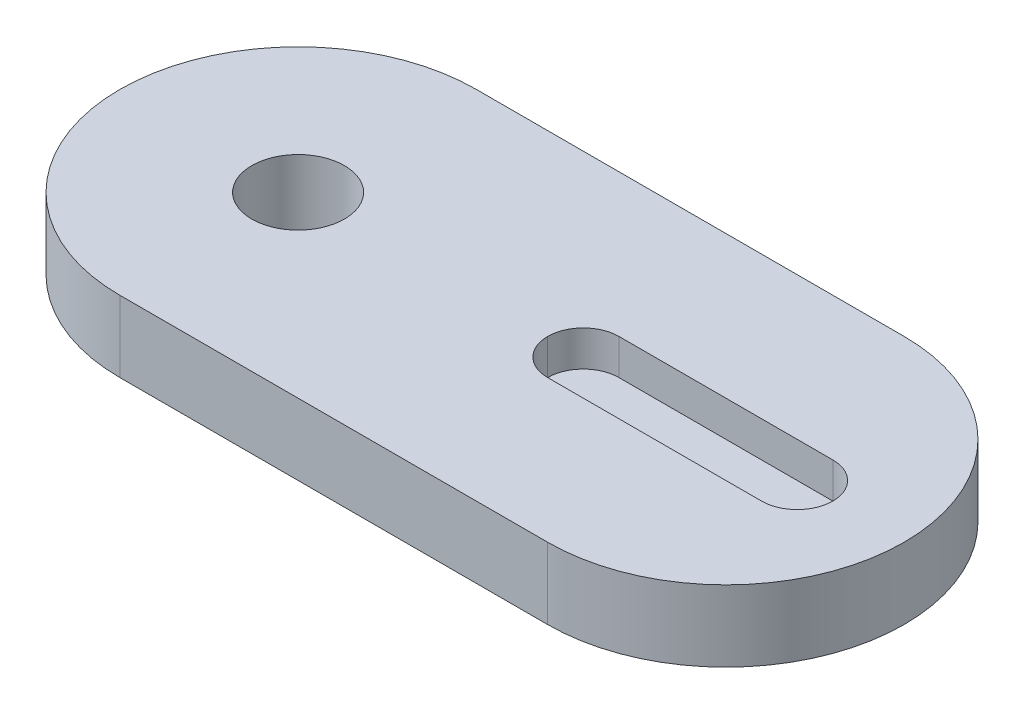
SolidWorks part; units mm, degrees
ref_plane "Front Plane" through (0, 0, 0) normal (0, 0, 1) x (1, 0, 0)
ref_plane "Top Plane" through (0, 0, 0) normal (0, 1, 0) x (1, 0, 0)
ref_plane "Right Plane" through (0, 0, 0) normal (1, 0, 0) x (0, 0, -1)
sketch "Sketch1" plane through (0, 0, 0) normal (0, 1, 0) x (1, 0, 0)
  line L0 (0, 6.35) -> (15.24, 6.35)
  line L1 (0, -6.35) -> (15.24, -6.35)
  arc A2 (0, 6.35) -> (0, -6.35) centre (0, 0) ccw
  arc A3 (15.24, -6.35) -> (15.24, 6.35) centre (15.24, 0) ccw
  dimension "D1" = 12.7
  dimension "D2" = 12.7
  dimension "D3" = 15.24
extrude "Boss-Extrude1" add sketch "Sketch1" along normal blind 2.54
sketch "Sketch2" plane through (0, 2.54, 0) normal (0, 1, 0) x (1, 0, 0)
  circle A0 centre (0, 0) radius 1.651
  dimension "D1" = 3.302
extrude "Cut-Extrude1" cut sketch "Sketch2" against normal blind 2.54
sketch "Sketch3" plane through (0, 2.54, 0) normal (0, 1, 0) x (1, 0, 0)
  line L1 (8.89, 1.27) -> (19.05, 1.27)
  line L2 (8.89, 1.27) -> (8.89, -1.27)
  line L3 (8.89, -1.27) -> (19.05, -1.27)
  line L4 (19.05, 1.27) -> (19.05, -1.27)
  dimension "D1" = 2.54
  dimension "D2" = 10.16
  dimension "D3" = 1.27
  dimension "D4" = 8.89
extrude "Cut-Extrude2" cut sketch "Sketch3" against normal blind 1.27
fillet "Fillet1" radius 1.27 4 edges at (19.05, 1.905, 1.27) (19.05, 1.905, -1.27) (8.89, 1.905, 1.27) (8.89, 1.905, -1.27)
